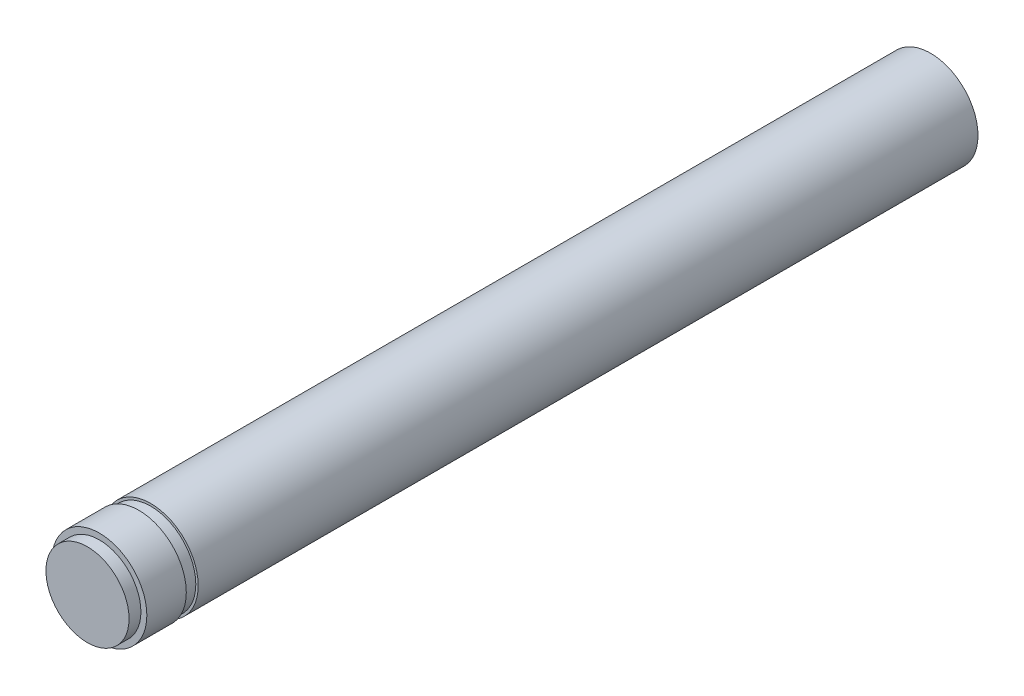
SolidWorks part; units mm, degrees
material "AISI 316 Annealed Stainless Steel Bar (SS)"
ref_plane "Front Plane" through (0, 0, 0) normal (0, 0, 1) x (1, 0, 0)
ref_plane "Top Plane" through (0, 0, 0) normal (0, 1, 0) x (1, 0, 0)
ref_plane "Right Plane" through (0, 0, 0) normal (1, 0, 0) x (0, 0, -1)
ref_axis "Z" through (0, 0, -3.55) along (0, 0, 1)
sketch "Sketch2" plane through (0, 0, 0) normal (0, 1, 0) x (1, 0, 0)
  line L0 (0, 0) -> (0, -70)
  line L1 (0, 0) -> (4, 0)
  line L2 (0, -25.9144) -> (0, 43.7641) construction
  line L3 (4, 0) -> (4, -65.6762)
  line L4 (4, -70) -> (0, -70) construction
  line L5 (3.5, -70) -> (3.5, -71)
  line L6 (3.5, -71) -> (0, -71)
  line L7 (0, -71) -> (0, -70)
  line L8 (3.5, -70) -> (4, -70)
  line L9 (4, -66.6762) -> (3.8, -66.6762)
  line L10 (3.8, -66.6762) -> (3.8, -65.6762)
  line L11 (3.8, -65.6762) -> (4, -65.6762)
  line L12 (4, -66.6762) -> (4, -70)
  line L13 (4, -65.6762) -> (4, -66.6762) construction
  dimension "D1" = 70
  dimension "D2" = 4
  dimension "D3" = 1
  dimension "D4" = 7
  dimension "D5" = 1
  dimension "D6" = 7.6
  dimension "D7" = 66.6762
revolve "Revolve1" add sketch "Sketch2" angle 360 about L2
